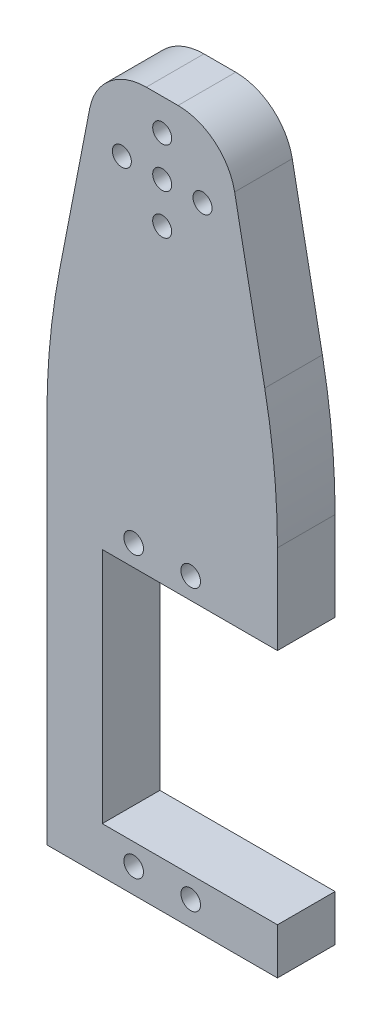
SolidWorks part; units mm, degrees
ref_plane "Front Plane" through (0, 0, 0) normal (0, 0, 1) x (1, 0, 0)
ref_plane "Top Plane" through (0, 0, 0) normal (0, 1, 0) x (1, 0, 0)
ref_plane "Right Plane" through (0, 0, 0) normal (1, 0, 0) x (0, 0, -1)
sketch "Sketch2" plane through (0, 0, 0) normal (0, 0, 1) x (1, 0, 0)
  line L1 (-40, 122.5) -> (0, 122.5)
  line L2 (-40, 122.5) -> (-40, 0)
  line L3 (-40, 0) -> (0, 0)
  line L4 (0, 122.5) -> (0, 0)
  dimension "D1" = 122.5
  dimension "D2" = 40
extrude "Boss-Extrude1" add sketch "Sketch2" along normal blind 10
sketch "Sketch3" plane through (0, 0, 0) normal (0, 0, 1) x (1, 0, 0)
  line L0 (-30.4, 8) -> (-9.6, 8)
  line L2 (-9.6, 8) -> (-9.6, 49.2)
  line L3 (-15.05, 52.9) -> (-24.95, 52.9) construction
  line L4 (-30.4, 8) -> (-30.4, 4.3) construction
  line L9 (-30.4, 4.3) -> (-24.95, 4.3) construction
  line L11 (-9.6, 49.2) -> (-30.4, 49.2)
  line L12 (-30.4, 49.2) -> (-30.4, 8)
  line L14 (-40, 122.5) -> (-40, 0) construction
  line L15 (0, 0) -> (0, 122.5) construction
  circle A0 centre (-24.95, 4.3) radius 1.7
  circle A1 centre (-15.05, 4.3) radius 1.7
  circle A2 centre (-15.05, 52.9) radius 1.7
  circle A3 centre (-24.95, 52.9) radius 1.7
  point P0 (-20, 8)
  point P4 (-20, 49.2)
  dimension "D7" = 3.4
  dimension "D13" = 3.4
  dimension "D1" = 41.2
  dimension "D4" = 3.7
  dimension "D5" = 9.9
  dimension "D2" = 3.7
  dimension "D9" = 9.9
  dimension "D10" = 4.95
  dimension "D11" = 4.95
  dimension "D12" = 8
  dimension "D8" = 3.7
  dimension "D3" = 20.8
  dimension "D6" = 40
  dimension "D14" = 20
extrude "Cut-Extrude3" cut sketch "Sketch3" along normal through all contours A1 | A0 | A2 | L12 L0 L2 L11 | A3
sketch "Sketch4" plane through (0, 0, 10) normal (0, 0, 1) x (1, 0, 0)
  line L4 (-40, 122.5) -> (-40, 0) construction
  line L5 (0, 0) -> (0, 122.5) construction
  circle A0 centre (-20, 110) radius 1.65
  circle A1 centre (-20, 110) radius 7 construction
  circle A2 centre (-27, 110) radius 1.65
  circle A3 centre (-20, 117) radius 1.65
  circle A4 centre (-13, 110) radius 1.65
  circle A5 centre (-20, 103) radius 1.65
  dimension "D2" = 3.3
  dimension "D3" = 14
  dimension "D5" = 110
  dimension "D4" = 20
extrude "Cut-Extrude4" cut sketch "Sketch4" against normal through all
sketch "Sketch5" plane through (0, 0, 10) normal (0, 0, 1) x (1, 0, 0)
  line L0 (0, -5.5) -> (0, 5.5) construction
  line L1 (-30.4, 8) -> (0, 8)
  line L2 (-30.4, 8) -> (-30.4, 49.2)
  line L3 (-30.4, 49.2) -> (0, 49.2)
  line L4 (0, 8) -> (0, 49.2)
  line L6 (-40, 122.5) -> (-31, 122.5)
  line L7 (-40, 122.5) -> (-40, 70)
  line L8 (-40, 70) -> (-31, 70)
  line L9 (-31, 122.5) -> (-31, 70)
  line L10 (0, 122.5) -> (-9, 122.5)
  line L11 (0, 122.5) -> (0, 70)
  line L12 (0, 70) -> (-9, 70)
  line L13 (-9, 122.5) -> (-9, 70)
  dimension "D1" = 41.2
  dimension "D2" = 52.5
  dimension "D3" = 9
extrude "Cut-Extrude5" cut sketch "Sketch5" against normal through all
draft "Draft11" type of draft neutral plane draft angle 11 faces to draft 2 face at (-9, 96.25, 5) face at (-31, 96.25, 5) neutral plane through (-40, 122.5, 10) neutral plane normal (0, 1, 0) parameters "D1"=11
fillet "Fillet4" radius 120 2 edges at (-40, 76.199, 5) (0, 76.199, 5)
fillet "Fillet5" radius 10 2 edges at (-31, 122.5, 5) (-9, 122.5, 5)
equation "\"D10@Sketch3\"=\"D9@Sketch3\"/2"
equation "\"D11@Sketch3\"=\"D5@Sketch3\"/2"
equation "\"D4@Sketch4\"=\"D1@Sketch4\"/2"
equation "\"D14@Sketch3\"=\"D6@Sketch3\"/2"
